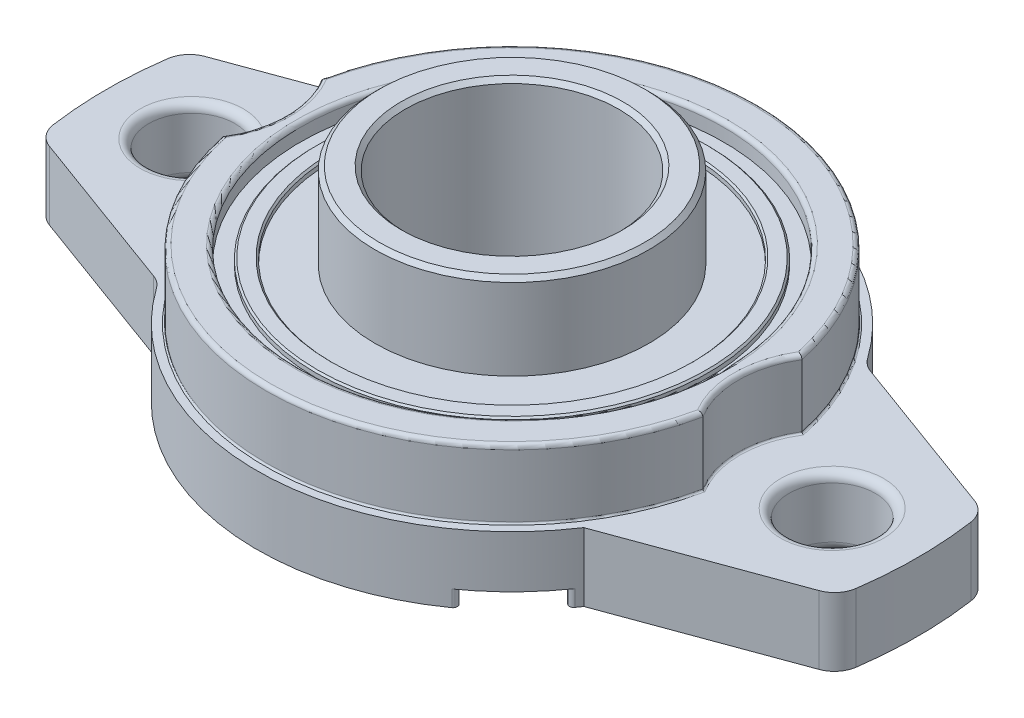
SolidWorks part; units mm, degrees
ref_plane "Front Plane" through (0, 0, 0) normal (0, 0, 1) x (1, 0, 0)
ref_plane "Top Plane" through (0, 0, 0) normal (0, 1, 0) x (1, 0, 0)
ref_plane "Right Plane" through (0, 0, 0) normal (1, 0, 0) x (0, 0, -1)
sketch "Sketch1" plane through (0, 0, 0) normal (0, 1, 0) x (1, 0, 0)
  line L0 (-46.7333, 8.5) -> (-24.9051, 16.5)
  line L1 (-46.7333, -8.5) -> (-24.9051, -16.5)
  line L2 (0, 0) -> (0, 12.5) construction
  line L3 (46.7333, -8.5) -> (24.9051, -16.5)
  line L4 (46.7333, 8.5) -> (24.9051, 16.5)
  line L7 (-47.5, 0) -> (0, 0) construction
  circle A0 centre (0, 0) radius 12.5
  arc A1 (-24.9051, -16.5) -> (24.9051, -16.5) centre (0, 0) ccw
  circle A2 centre (-37.5, 0) radius 5.05
  arc A3 (-46.7333, 8.5) -> (-46.7333, -8.5) centre (0, 0) ccw
  arc A4 (46.7333, 8.5) -> (46.7333, -8.5) centre (0, 0) cw
  circle A5 centre (37.5, 0) radius 5.05
  arc A6 (24.9051, 16.5) -> (-24.9051, 16.5) centre (0, 0) ccw
  dimension "D1" = 25
  dimension "D2" = 59.75
  dimension "D6" = 10.1
  dimension "D5" = 16.5
  dimension "D7" = 10
extrude "Boss-Extrude1" add sketch "Sketch1" along normal blind 8
fillet "Fillet1" radius 1 4 edges at (37.5, 0, -5.05) (37.5, 8, -5.05) (-37.5, 0, 5.05) (-37.5, 8, 5.05)
sketch "Sketch2" plane through (0, 0, 0) normal (0, -1, 0) x (1, 0, 0)
  line L8 (42.6855, 5.1908) -> (21.9063, 12.8063)
  line L9 (-21.9063, 12.8063) -> (-42.6855, 5.1908)
  line L10 (-42.6855, -5.1908) -> (-21.9063, -12.8063)
  line L11 (21.9063, -12.8063) -> (42.6855, -5.1908)
  line L12 (31.6956, 9.2186) -> (21.9063, 12.8063)
  line L13 (-21.9063, 12.8063) -> (-31.6956, 9.2186)
  line L14 (-31.6956, -9.2186) -> (-21.9063, -12.8063)
  line L15 (21.9063, -12.8063) -> (31.6956, -9.2186)
  arc A4 (-32.3324, -5.8426) -> (-32.3324, 5.8426) centre (-37.5, 0) ccw
  arc A5 (32.3324, 5.8426) -> (32.3324, -5.8426) centre (37.5, 0) ccw
  arc A6 (32.3324, -5.8426) -> (31.6956, -9.2186) centre (31.0074, -7.3407) cw
  arc A7 (32.3324, 5.8426) -> (31.6956, 9.2186) centre (31.0074, 7.3407) ccw
  arc A8 (42.6855, -5.1908) -> (42.6855, 5.1908) centre (0, 0) ccw
  arc A9 (21.9063, 12.8063) -> (-21.9063, 12.8063) centre (0, 0) ccw
  arc A10 (-42.6855, 5.1908) -> (-42.6855, -5.1908) centre (0, 0) ccw
  arc A11 (-21.9063, -12.8063) -> (21.9063, -12.8063) centre (0, 0) ccw
  arc A12 (-32.3324, -5.8426) -> (-31.6956, -9.2186) centre (-31.0074, -7.3407) ccw
  arc A13 (21.9063, 12.8063) -> (-21.9063, 12.8063) centre (0, 0) ccw
  arc A14 (-32.3324, 5.8426) -> (-31.6956, 9.2186) centre (-31.0074, 7.3407) cw
  arc A15 (-21.9063, -12.8063) -> (21.9063, -12.8063) centre (0, 0) ccw
  dimension "D2" = 15.6
  dimension "D3" = 15.6
  dimension "D4" = 2
  dimension "D1" = 4.5
extrude "Cut-Extrude1" cut sketch "Sketch2" against normal blind 1.9
sketch "Sketch3" plane through (0, 0, 0) normal (0, -1, 0) x (1, 0, 0)
  line L0 (17.8009, 23.9926) -> (15.0693, 21.3539)
  line L1 (15.0693, 21.3539) -> (21.3222, 14.8808)
  line L2 (21.3222, 14.8808) -> (24.4149, 17.8683)
  line L3 (24.4149, 17.8683) -> (18.162, 24.3414)
  line L4 (18.162, 24.3414) -> (17.8009, 23.9926)
  line L5 (0, 0) -> (41.8186, 40.3962) construction
  line L6 (0, 0) -> (-4.1964, 4.3442) construction
  line L7 (-24.955, -17.3091) -> (-24.594, -16.9603)
  line L8 (-15.6094, -20.7947) -> (-18.7021, -23.7822)
  line L9 (-18.7021, -23.7822) -> (-24.955, -17.3091)
  line L10 (-21.8623, -14.3216) -> (-15.6094, -20.7947)
  line L11 (-24.594, -16.9603) -> (-21.8623, -14.3216)
  arc A0 (24.9051, 16.5) -> (-24.9051, 16.5) centre (0, 0) ccw construction
  dimension "D1" = 9
  dimension "D2" = 4.3
extrude "Cut-Extrude2" cut sketch "Sketch3" against normal blind 1.9
fillet "Fillet2" radius 0.5 8 edges at (24.139, 0.95, 17.6018) (21.3222, 0.95, 14.8808) (17.8009, 0.95, 23.9926) (15.0693, 0.95, 21.3539) (-24.594, 0.95, -16.9603) (-18.4263, 0.95, -23.5157) (-15.6094, 0.95, -20.7947) (-21.8623, 0.95, -14.3216)
sketch "Sketch5" plane through (0, 1.9, 0) normal (0, -1, 0) x (1, 0, 0)
  circle A0 centre (0, 0) radius 23
  circle A1 centre (0, 0) radius 21
  dimension "D1" = 46
  dimension "D2" = 2
extrude "Boss-Extrude2" add sketch "Sketch5" along normal blind 0.3
sketch "Sketch6" plane through (0, 1.9, 0) normal (0, -1, 0) x (1, 0, 0)
  circle A0 centre (0, 0) radius 12.5
  circle A1 centre (0, 0) radius 16
  dimension "D1" = 32
extrude "Boss-Extrude3" add sketch "Sketch6" along normal blind 1.4
chamfer "Chamfer1" distance 0.5 angle 45 2 edges at (0, 0.5, -12.5) (0, 0.5, -16)
fillet "Fillet3" radius 3 6 edges at (-21.9063, 0.95, -12.8063) (21.9063, 0.95, 12.8063) (21.9063, 0.95, -12.8063) (24.9051, 4, -16.5) (-24.9051, 4, 16.5) (-21.9063, 0.95, 12.8063)
sketch "Sketch7" plane through (0, 1.9, 0) normal (0, -1, 0) x (1, 0, 0)
  line L0 (0, 0) -> (-29.1527, 29.3328) construction
  line L1 (-21.1785, 8.9706) -> (-22.6978, 9.6142)
  line L2 (-9.0996, 21.1234) -> (-9.7524, 22.6388)
  line L3 (0, 0) -> (6.0581, 6.0209) construction
  line L4 (21.0669, -9.2295) -> (22.5783, -9.8917)
  line L5 (8.84, -21.2333) -> (9.4742, -22.7566)
  arc A0 (-9.0996, 21.1234) -> (-21.1785, 8.9706) centre (0, 0) ccw
  arc A1 (-9.7524, 22.6388) -> (-22.6978, 9.6142) centre (0, 0) ccw
  arc A2 (22.5783, -9.8917) -> (9.4742, -22.7566) centre (0, 0) cw
  arc A3 (21.0669, -9.2295) -> (8.84, -21.2333) centre (0, 0) cw
  dimension "D1" = 49.3
extrude "Cut-Extrude3" cut sketch "Sketch7" against normal through all
sketch "Sketch8" plane through (0, 0, 0) normal (0, -1, 0) x (1, 0, 0)
  line L5 (14.0393, 23.1397) -> (15.2595, 20.8424)
  line L6 (13.9782, 19.6047) -> (19.5363, 13.8508)
  line L7 (13.9782, 19.6047) -> (19.5363, 13.8508)
  line L8 (15.2595, 20.8424) -> (21.6013, 14.044)
  line L9 (21.6013, 14.044) -> (23.0713, 13.7897)
  line L10 (18.1957, 18.1173) -> (0, 0) construction
  line L11 (15.4166, 20.9942) -> (20.9748, 15.2404) construction
  line L12 (0, 0) -> (-5.2936, 5.3165) construction
  line L15 (-23.6115, -13.2305) -> (-21.0359, -14.7584)
  line L16 (-14.5183, -19.0455) -> (-20.0765, -13.2917)
  line L17 (-14.5183, -19.0455) -> (-20.0765, -13.2917)
  line L18 (-21.0359, -14.7584) -> (-15.323, -20.9783)
  line L19 (-15.323, -20.9783) -> (-14.5795, -22.5805)
  arc A9 (19.5363, 13.8508) -> (23.0713, 13.7897) centre (21.3344, 15.5878) ccw
  arc A10 (14.0393, 23.1397) -> (13.9782, 19.6047) centre (15.7763, 21.3416) ccw
  arc A11 (19.5363, 13.8508) -> (23.0713, 13.7897) centre (21.3344, 15.5878) ccw
  arc A12 (14.0393, 23.1397) -> (13.9782, 19.6047) centre (15.7763, 21.3416) ccw
  arc A17 (-14.5795, -22.5805) -> (-14.5183, -19.0455) centre (-16.3164, -20.7824) ccw
  arc A18 (-20.0765, -13.2917) -> (-23.6115, -13.2305) centre (-21.8746, -15.0286) ccw
  arc A19 (-14.5795, -22.5805) -> (-14.5183, -19.0455) centre (-16.3164, -20.7824) ccw
  arc A20 (-20.0765, -13.2917) -> (-23.6115, -13.2305) centre (-21.8746, -15.0286) ccw
  dimension "D1" = 2
  dimension "D2" = 2
extrude "Boss-Extrude4" add sketch "Sketch8" against normal blind 2
fillet "Fillet4" radius 3 4 edges at (46.7333, 4, -8.5) (46.7333, 4, 8.5) (-46.7333, 4, -8.5) (-46.7333, 4, 8.5)
sketch "Sketch9" plane through (0, 8, 0) normal (0, 1, 0) x (1, 0, 0)
  circle A0 centre (0, 0) radius 28.75
  circle A1 centre (0, 0) radius 12.5
  dimension "D1" = 57.5
extrude "Boss-Extrude5" add sketch "Sketch9" along normal blind 8
sketch "Sketch10" plane through (0, 16, 0) normal (0, 1, 0) x (1, 0, 0)
  circle A0 centre (0, 0) radius 24.8
  dimension "D1" = 49.6
extrude "Cut-Extrude4" cut sketch "Sketch10" against normal blind 2
sketch "Sketch11" plane through (0, 14, 0) normal (0, 1, 0) x (1, 0, 0)
  circle A0 centre (0, 0) radius 21
  circle A1 centre (0, 0) radius 23
  dimension "D1" = 46
  dimension "D2" = 42
extrude "Boss-Extrude6" add sketch "Sketch11" along normal blind 0.7
sketch "Sketch12" plane through (0, 14, 0) normal (0, 1, 0) x (1, 0, 0)
  circle A0 centre (0, 0) radius 12.5
  circle A1 centre (0, 0) radius 16.05
  dimension "D1" = 32.1
extrude "Boss-Extrude7" add sketch "Sketch12" along normal blind 10
chamfer "Chamfer2" distance 0.5 angle 45 2 edges at (0, 24, 12.5) (0, 24, 16.05)
chamfer "Chamfer3" distance 0.2 angle 45 2 edges at (0, 14.7, 21) (0, 14.7, 23)
sketch "Sketch13" plane through (0, 16, 0) normal (0, 1, 0) x (1, 0, 0)
  circle A0 centre (-37.5, 0) radius 11
  circle A1 centre (37.5, 0) radius 11
  dimension "D1" = 22
  dimension "D2" = 22
extrude "Cut-Extrude5" cut sketch "Sketch13" against normal up to surface (8 mm away) up to face at (0, 8, 0)
fillet "Fillet5" radius 0.5 5 edges at (0, 16, 24.8) (0, 16, 28.75) (-26.5, 16, 0) (0, 16, -28.75) (26.5, 16, 0)
fillet "Fillet6" radius 0.2 4 edges at (-26.5, 8, 0) (0, 8, -28.75) (26.5, 8, 0) (0, 8, 28.75)
